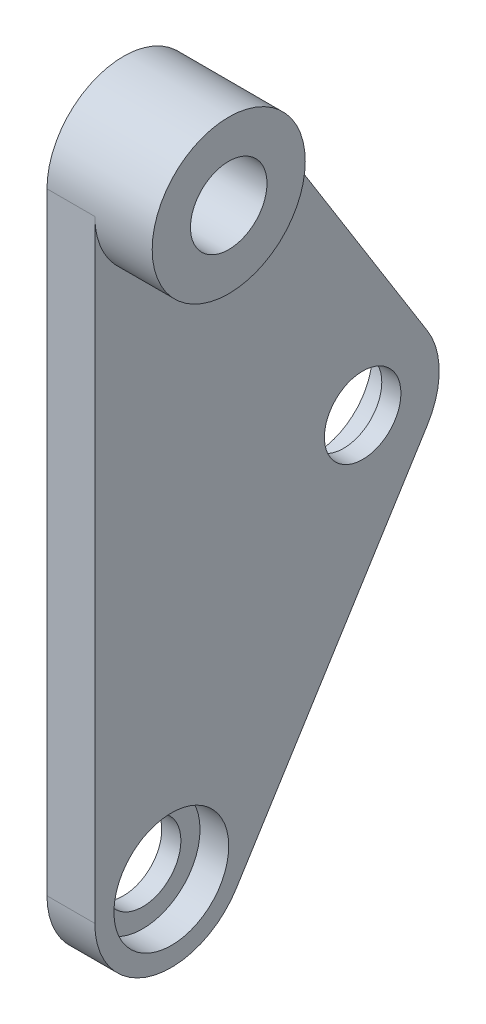
SolidWorks part; units mm, degrees
ref_plane "前视基准面" through (0, 0, 0) normal (0, 0, 1) x (1, 0, 0)
ref_plane "上视基准面" through (0, 0, 0) normal (0, 1, 0) x (1, 0, 0)
ref_plane "右视基准面" through (0, 0, 0) normal (1, 0, 0) x (0, 0, -1)
other "Configuration Table"
sketch "草图1" plane through (0, 0, 0) normal (1, 0, 0) x (0, 0, -1)
  line L0 (0, -20) -> (18, -20) construction
  line L1 (0, 0) -> (18, 0) construction
  line L2 (0, 0) -> (0, -40)
  line L3 (0, -40) -> (18, -40) construction
  line L4 (18, 0) -> (18, -40) construction
  line L5 (7.392, -1.88) -> (17.392, -17.88)
  line L6 (17.392, -22.12) -> (7.392, -38.12)
  circle A0 centre (4, -4) radius 4
  circle A1 centre (4, -36) radius 4
  circle A2 centre (14, -20) radius 4
  circle A3 centre (4, -4) radius 2
  circle A4 centre (14, -20) radius 2
  circle A5 centre (4, -36) radius 2
  dimension "D1" = 8
  dimension "D2" = 4
  dimension "D3" = 40
  dimension "D4" = 18
extrude "凸台-拉伸1" add sketch "草图1" along normal blind 2.5 contours A2 L5 A0 L2 A1 L6 | A0 | A2 | A1 region at (0, -20, -6.5849)
extrude "凸台-拉伸2" add sketch "草图1<4>" against normal blind 3 contours A0
sketch "草图1<4>" plane through (0, 0, 0) normal (1, 0, 0) x (0, 0, -1) same geometry as "草图1"
extrude "切除-拉伸1" cut sketch "草图1<3>" along normal through all both and the other way through all contours A3 | A4 | A5
sketch "草图1<3>" plane through (0, 0, 0) normal (1, 0, 0) x (0, 0, -1) same geometry as "草图1"
sketch "草图2" plane through (2.5, 0, 0) normal (1, 0, 0) x (0, 0, -1)
  circle A0 centre (4, -4) radius 3
  circle A1 centre (14, -20) radius 3
  circle A2 centre (4, -36) radius 3
  circle M3 centre (4, -4) radius 2
  arc M9 (7.392, -1.88) -> (0, -4) centre (4, -4) ccw
  dimension "D1" = 6
extrude "切除-拉伸2" cut sketch "草图2" against normal blind 1.5 contours A0 M9 M3 | A1 region at (2.5, -4, -1.0849)
extrude "切除-拉伸3" cut sketch "草图2<3>" along normal blind 1.5 from surface contours A2 starting at face at (0, -20, -16)
sketch "草图2<3>" plane through (2.5, 0, 0) normal (1, 0, 0) x (0, 0, -1) same geometry as "草图2"
ref_plane "基准面1" through (-10, 0, 0) normal (1, 0, 0) x (0, 0, -1)
mirror "镜向2" about plane through (-10, 0, 0) normal (1, 0, 0) of bodies 111 109
sketch "草图3" plane through (0, 0, 0) normal (0, 0, 1) x (1, 0, 0)
  line L1 (-9.0746, 6.6499) -> (12.7517, 6.6499)
  line L2 (-9.0746, 6.6499) -> (-9.0746, -49.8319)
  line L3 (-9.0746, -49.8319) -> (12.7517, -49.8319)
  line L4 (12.7517, 6.6499) -> (12.7517, -49.8319)
extrude "切除-拉伸4" cut sketch "草图3" against normal through all
